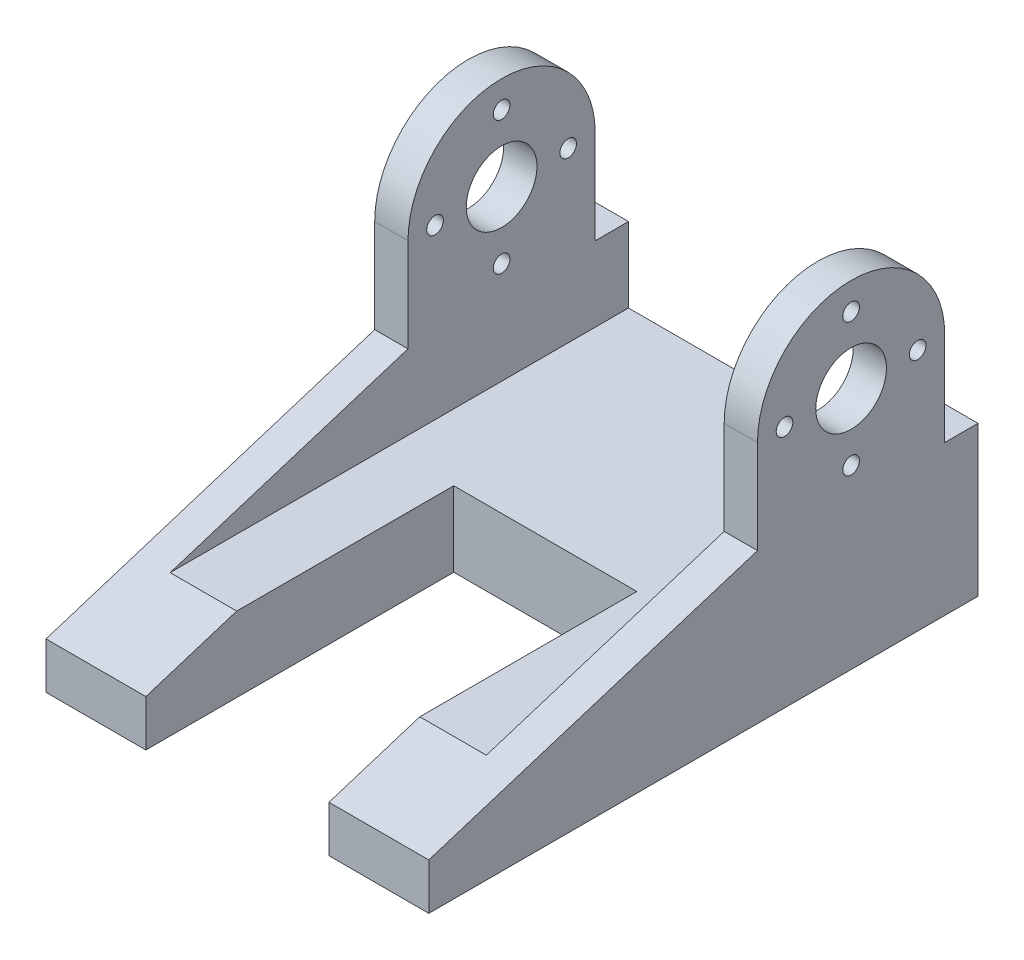
SolidWorks part; units mm, degrees
ref_plane "Front Plane" through (0, 0, 0) normal (0, 0, 1) x (1, 0, 0)
ref_plane "Top Plane" through (0, 0, 0) normal (0, 1, 0) x (1, 0, 0)
ref_plane "Right Plane" through (0, 0, 0) normal (1, 0, 0) x (0, 0, -1)
sketch "Sketch1" plane through (0, 0, 0) normal (0, 0, 1) x (1, 0, 0)
  line L1 (-25, 0) -> (25, 0)
  line L2 (-25, 0) -> (-25, -170)
  line L3 (-25, -170) -> (25, -170)
  line L4 (25, 0) -> (25, -170)
  dimension "D1" = 170
  dimension "D2" = 50
extrude "Boss-Extrude1" add sketch "Sketch1" against normal blind 55
sketch "Sketch2" plane through (0, 0, 0) normal (0, 0, 1) x (1, 0, 0)
  line L0 (25, 0) -> (-25, 0) construction
  line L1 (-17, 0) -> (17, 0)
  line L2 (-17, 0) -> (-17, -27)
  line L3 (-17, -27) -> (17, -27)
  line L4 (17, 0) -> (17, -27)
  line L5 (-25, 0) -> (-25, -170) construction
  dimension "D1" = 8
  dimension "D2" = 34
  dimension "D3" = 27
extrude "Cut-Extrude1" cut sketch "Sketch2" against normal through all
sketch "Sketch3" plane through (25, 0, 0) normal (1, 0, 0) x (0, 0, -1)
  line L0 (0, -170) -> (0, 0) construction
  line L1 (55, -27) -> (0, -27)
  line L2 (55, -27) -> (55, -24)
  line L3 (55, -24) -> (0, -24)
  line L4 (0, -27) -> (0, -24)
  line L5 (55, -170) -> (55, 0) construction
  line L7 (0, 0) -> (10, 0)
  line L8 (0, 0) -> (0, -24)
  line L9 (0, -24) -> (10, -24)
  line L10 (10, 0) -> (10, -24)
  line L11 (55, 0) -> (45, 0)
  line L12 (55, 0) -> (55, -24)
  line L13 (55, -24) -> (45, -24)
  line L14 (45, 0) -> (45, -24)
  circle A0 centre (27.5, -12.75) radius 10.25
  circle A1 centre (27.5, -12.75) radius 4.25
  circle A2 centre (27.5, -12.75) radius 8
  circle A3 centre (27.5, -4.75) radius 1
  circle A4 centre (35.5, -12.75) radius 1
  circle A5 centre (27.5, -20.75) radius 1
  circle A6 centre (19.5, -12.75) radius 1
  point P32 (27.5, -12.75)
  line M7 (0, 0) -> (0, -170)
  line M9 (55, -170) -> (55, 0)
  line M10 (55, 0) -> (0, 0)
  dimension "D2" = 11.25
  dimension "D3" = 27.5
  dimension "D4" = 20.5
  dimension "D7" = 8.5
  dimension "D8" = 16
  dimension "D9" = 4
  dimension "D1" = 3
  dimension "D5" = 10
  dimension "D6" = 10
extrude "Cut-Extrude2" cut sketch "Sketch3" against normal through all contours L14 L3 M10 M9 | L10 L3 M10 M7 | A2 A6 | A2 A6 | A1 | A2 A5 | A2 A5 | A2 A4 | A2 A4 | A2 A3 | A2 A3 region at (25, -12, -50) region at (25, -12, -5) region at (25, -12.75, -27.5) region at (25, -12.75, -35.0645) region at (25, -12.75, -35.913) region at (25, -5.1855, -27.5) region at (25, -4.337, -27.5) region at (25, -21.163, -27.5) region at (25, -20.3145, -27.5) region at (25, -12.75, -19.9355) region at (25, -12.75, -19.087)
sketch "Sketch4" plane through (0, 0, -10) normal (0, 0, 1) x (1, 0, 0)
  line L0 (-25, -24) -> (-17, -24) construction
  line L1 (-17, 0) -> (-19, 0)
  line L2 (-17, 0) -> (-17, -24)
  line L3 (-17, -24) -> (-19, -24)
  line L4 (-19, 0) -> (-19, -24)
  line L5 (0, 0) -> (0, -13.53) construction
  line L6 (19, 0) -> (19, -24)
  line L7 (17, -24) -> (19, -24)
  line L8 (17, 0) -> (17, -24)
  line L9 (17, 0) -> (19, 0)
  dimension "D1" = 2
extrude "Cut-Extrude3" cut sketch "Sketch4" against normal through all
sketch "Sketch5" plane through (25, 0, 0) normal (1, 0, 0) x (0, 0, -1)
  line L1 (10, 0) -> (45, 0)
  line L2 (10, 0) -> (10, -24)
  line L3 (10, -24) -> (45, -24)
  line L4 (45, 0) -> (45, -24)
  line L5 (38.75, -12.75) -> (38.75, -24)
  line L6 (16.25, -12.75) -> (10, -12.75)
  line L7 (16.25, -12.75) -> (16.25, -24)
  line L8 (16.25, -24) -> (10, -24)
  line L9 (10, -12.75) -> (10, -24)
  line L10 (38.75, -12.75) -> (45, -12.75)
  line L11 (38.75, -12.75) -> (38.75, -24)
  line L12 (38.75, -24) -> (45, -24)
  line L13 (45, -12.75) -> (45, -24)
  circle A0 centre (27.5, -12.75) radius 11.25
  line M8 (45, -24) -> (45, 0)
  line M9 (45, 0) -> (10, 0)
  line M10 (10, 0) -> (10, -24)
  dimension "D1" = 22.5
extrude "Cut-Extrude4" cut sketch "Sketch5" against normal through all contours A0 L10 L4 L6 M9 M10 | L7 L6 L2 L3 | L10 L5 L3 M8 region at (25, -0.3725, -27.5) region at (25, -18.375, -13.125) region at (25, -18.375, -41.875)
sketch "Sketch6" plane through (0, 0, 0) normal (0, 0, 1) x (1, 0, 0)
  line L1 (-19, -24) -> (19, -24)
  line L2 (-19, -24) -> (-19, -34)
  line L3 (-19, -34) -> (19, -34)
  line L4 (19, -24) -> (19, -34)
  dimension "D1" = 10
extrude "Cut-Extrude5" cut sketch "Sketch6" against normal through all
sketch "Sketch8" plane through (25, 0, 0) normal (1, 0, 0) x (0, 0, -1)
  line L0 (55, -170) -> (55, -24) construction
  line L1 (0, -170) -> (0, -24) construction
  line L2 (41.75, -132.5) -> (13.25, -132.5)
  line L3 (27.5, -132.5) -> (27.5, -179)
  line L4 (41.75, -179) -> (13.25, -179)
  line L5 (13.25, -132.5) -> (13.25, -179)
  line L7 (41.75, -132.5) -> (41.75, -179)
  line L11 (27.5, -167.75) -> (55, -167.75)
  line L12 (27.5, -167.75) -> (27.5, -170)
  line L13 (27.5, -170) -> (55, -170)
  line L14 (55, -167.75) -> (55, -170)
  line L16 (27.5, -167.75) -> (0, -167.75)
  line L17 (27.5, -167.75) -> (27.5, -170)
  line L18 (27.5, -170) -> (0, -170)
  line L19 (0, -167.75) -> (0, -170)
  circle A0 centre (27.5, -167.75) radius 10.25
  circle A1 centre (27.5, -12.75) radius 10.25
  line M4 (0, -24) -> (0, -170)
  line M5 (0, -170) -> (55, -170)
  line M6 (55, -170) -> (55, -24)
  dimension "D1" = 27.5
  dimension "D2" = 20.5
  dimension "D3" = 155
  dimension "D4" = 14.25
  dimension "D5" = 11.25
  dimension "D6" = 46.5
  dimension "D7" = 13.25
extrude "Cut-Extrude7" cut sketch "Sketch8" against normal through all contours A0 L3 L2 L5 L16 | A0 L11 L7 L2 L3 | L11 L7 M5 M6 | L5 L16 M4 M5 | A0 L16 L5 M5 | A0 L13 L7 L11 | L3 A0 L16 | L11 A0 L3 | L16 A0 L18 L3 | A0 L11 L3 M5 region at (25, -147.5157, -35.1704) region at (25, -147.5157, -19.8296) region at (25, -168.875, -48.375) region at (25, -168.8865, -39.7079) region at (25, -163.3998, -31.8502) region at (25, -163.3998, -23.1498) region at (25, -168.8704, -32.5838) region at (25, -168.8865, -15.2921) region at (25, -168.875, -6.625) region at (25, -168.8704, -22.4162)
sketch "Sketch9" plane through (0, 0, 0) normal (0, 0, 1) x (1, 0, 0)
  line L0 (-25, -167.75) -> (25, -167.75) construction
  line L1 (17, -167.75) -> (-17, -167.75)
  line L2 (17, -167.75) -> (17, -132.5)
  line L3 (17, -132.5) -> (-17, -132.5)
  line L4 (-17, -167.75) -> (-17, -132.5)
  line L5 (-25, -132.5) -> (25, -132.5) construction
  line L7 (-25, -24) -> (-25, -167.75) construction
  line L9 (25, -167.75) -> (25, -24) construction
  dimension "D1" = 8
  dimension "D2" = 8
extrude "Cut-Extrude8" cut sketch "Sketch9" against normal through all
sketch "Sketch11" plane through (25, 0, 0) normal (1, 0, 0) x (0, 0, -1)
  line L0 (27.5, -157.5) -> (27.5, -147.5)
  line L2 (27.5, -147.5) -> (55, -147.5)
  line L3 (27.5, -147.5) -> (27.5, -167.75)
  line L4 (27.5, -167.75) -> (55, -167.75)
  line L5 (55, -147.5) -> (55, -167.75)
  line L6 (27.5, -147.5) -> (0, -147.5)
  line L7 (27.5, -147.5) -> (27.5, -167.75)
  line L8 (27.5, -167.75) -> (0, -167.75)
  line L9 (0, -147.5) -> (0, -167.75)
  circle A0 centre (27.5, -167.75) radius 10.25
  arc A1 (38.75, -12.75) -> (16.25, -12.75) centre (27.5, -12.75) ccw construction
  line M1 (0, -167.75) -> (13.25, -167.75)
  line M2 (13.25, -167.75) -> (13.25, -132.5)
  line M4 (41.75, -132.5) -> (41.75, -167.75)
  line M5 (41.75, -167.75) -> (55, -167.75)
  line M6 (55, -167.75) -> (55, -24)
  line M12 (0, -24) -> (0, -167.75)
  dimension "D1" = 155
  dimension "D2" = 20.5
  dimension "D3" = 10
extrude "Cut-Extrude9" cut sketch "Sketch11" against normal through all contours A0 L0 L6 L8 M2 | A0 L4 L2 L0 M4 | L2 M4 M5 M6 | L6 M2 M12 M1 region at (25, -155.3124, -19.2638) region at (25, -155.3124, -35.7362) region at (25, -157.625, -48.375) region at (25, -157.625, -6.625)
sketch "Sketch12" plane through (25, 0, 0) normal (1, 0, 0) x (0, 0, -1)
  line L1 (13.25, -132.5) -> (41.75, -132.5)
  line L2 (13.25, -132.5) -> (13.25, -147.5)
  line L3 (13.25, -147.5) -> (41.75, -147.5)
  line L4 (41.75, -132.5) -> (41.75, -147.5)
extrude "Boss-Extrude2" add sketch "Sketch12" against normal blind 8
ref_plane "Plane1" through (0, 0, 0) normal (1, 0, 0) x (0, 0, -1)
mirror "Mirror1" about plane through (0, 0, 0) normal (1, 0, 0) of "Boss-Extrude2"
sketch "Sketch14" plane through (0, 0, 0) normal (0, 0, 1) x (1, 0, 0)
  line L0 (17, -148.55) -> (17, -158.75) construction
  line L1 (-17, -132.5) -> (17, -132.5)
  line L2 (-17, -132.5) -> (-17, -147.5)
  line L3 (-17, -147.5) -> (17, -147.5)
  line L4 (17, -132.5) -> (17, -147.5)
  line L5 (-17, -147.5) -> (17, -147.5)
  line L6 (-17, -147.5) -> (-17, -157.75)
  line L7 (-17, -157.75) -> (17, -157.75)
  line L8 (17, -147.5) -> (17, -157.75)
  line M11 (-17, -147.5) -> (-17, -132.5)
  line M12 (-17, -132.5) -> (17, -132.5)
  line M13 (17, -132.5) -> (17, -147.5)
  dimension "D1" = 10.25
extrude "Boss-Extrude3" add sketch "Sketch14" against normal blind 13.25 contours L3 M11 M13 M12 | L8 L3 L6 L7 region at (0, -140, 0) region at (0, -152.625, 0)
ref_plane "Plane2" through (0, 0, -27.5) normal (0, 0, 1) x (1, 0, 0)
mirror "Mirror2" about plane through (0, 0, -27.5) normal (0, 0, 1) of "Boss-Extrude3"
sketch "Sketch16" plane through (25, 0, 0) normal (1, 0, 0) x (0, 0, -1)
  line L0 (41.75, -132.5) -> (13.25, -132.5) construction
  line L1 (13.25, -132.5) -> (13.25, -147.5) construction
  circle A1 centre (16.5, -135.75) radius 2.5
  circle A2 centre (16.5, -135.75) radius 4.5
  circle A3 centre (38.5, -135.75) radius 4.5
  dimension "D1" = 3.25
  dimension "D2" = 3.25
  dimension "D3" = 2
extrude "Cut-Extrude13" cut sketch "Sketch16" against normal blind 8 contours A1 | A2 A1 | A3 region at (25, -135.75, -16.5) region at (25, -135.75, -12.1273) region at (25, -135.75, -38.5)
mirror "Mirror3" about plane through (0, 0, 0) normal (1, 0, 0) of "Cut-Extrude13"
sketch "Sketch17" plane through (25, 0, 0) normal (1, 0, 0) x (0, 0, -1)
  line L0 (55, -147.5) -> (55, -24) construction
  line L1 (27.5, -1.5) -> (55, -1.5)
  line L2 (27.5, -1.5) -> (27.5, -51.5)
  line L3 (27.5, -51.5) -> (55, -51.5)
  line L4 (55, -1.5) -> (55, -51.5)
  line L8 (55, -51.5) -> (0, -51.5)
  line L9 (55, -51.5) -> (55, -157.75)
  line L10 (55, -157.75) -> (0, -157.75)
  line L11 (0, -51.5) -> (0, -157.75)
  arc A0 (38.75, -12.75) -> (16.25, -12.75) centre (27.5, -12.75) ccw construction
  circle M2 centre (16.5, -135.75) radius 4.5
  circle M3 centre (38.5, -135.75) radius 4.5
  line M4 (0, -147.5) -> (55, -147.5)
  line M5 (55, -147.5) -> (55, -24)
  line M11 (0, -24) -> (0, -147.5)
  dimension "D1" = 50
extrude "Cut-Extrude15" cut sketch "Sketch17" against normal through all contours L3 L8 M11 M4 M5 M2 M3 | L11 L10 L9 M4 | M3 | M2 region at (25, -98.6049, -27.5) region at (25, -152.625, -27.5) region at (25, -135.75, -16.5) region at (25, -135.75, -38.5)
sketch "Sketch18" plane through (25, 0, 0) normal (1, 0, 0) x (0, 0, -1)
  line L1 (38.75, -24) -> (-71.25, -24)
  line L2 (38.75, -24) -> (38.75, -51.5)
  line L3 (38.75, -51.5) -> (-71.25, -51.5)
  line L4 (-71.25, -24) -> (-71.25, -51.5)
  line L6 (38.75, -24) -> (68.75, -24)
  line L7 (38.75, -24) -> (38.75, -51.5)
  line L8 (38.75, -51.5) -> (68.75, -51.5)
  line L9 (68.75, -24) -> (68.75, -51.5)
  line M8 (0, -24) -> (0, -51.5)
  line M9 (0, -51.5) -> (55, -51.5)
  line M10 (55, -51.5) -> (55, -24)
  line M11 (55, -24) -> (38.75, -24)
  line M15 (16.25, -24) -> (0, -24)
  dimension "D1" = 110
  dimension "D2" = 30
extrude "Boss-Extrude4" add sketch "Sketch18" against normal blind 50 contours L1 L4 L3 M8 | L9 L6 L8 M10 | L2 L1 M15 M8 M9 | L2 M11 M9 M10 region at (25, -37.75, -19.375) region at (25, -37.75, -46.875) region at (25, -37.75, -61.875) region at (25, -37.75, 35.625)
sketch "Sketch19" plane through (0, 0, 71.25) normal (0, 0, 1) x (1, 0, 0)
  line L1 (-19, -24) -> (19, -24)
  line L2 (-19, -24) -> (-19, -31)
  line L3 (-19, -31) -> (19, -31)
  line L4 (19, -24) -> (19, -31)
  dimension "D1" = 7
extrude "Cut-Extrude16" cut sketch "Sketch19" against normal through all
sketch "Sketch20" plane through (25, 0, 0) normal (1, 0, 0) x (0, 0, -1)
  line L1 (-71.25, -24) -> (68.75, -24)
  line L2 (-71.25, -24) -> (-71.25, -51.5)
  line L3 (-71.25, -51.5) -> (68.75, -51.5)
  line L4 (68.75, -24) -> (68.75, -51.5)
  line L5 (16.25, -24) -> (-13.75, -24)
  line L6 (16.25, -24) -> (16.25, -51.5)
  line L7 (16.25, -51.5) -> (-13.75, -51.5)
  line L8 (-13.75, -24) -> (-13.75, -51.5)
  line L10 (-13.75, -51.5) -> (-71.25, -51.5)
  line L11 (-13.75, -51.5) -> (-13.75, -24)
  line L12 (-13.75, -24) -> (-71.25, -24)
  line L13 (-71.25, -51.5) -> (-71.25, -24)
  line M8 (-71.25, -24) -> (-71.25, -51.5)
  line M9 (-71.25, -51.5) -> (68.75, -51.5)
  dimension "D1" = 30
extrude "Cut-Extrude17" cut sketch "Sketch20" against normal through all contours L8 L1 M8 M9 region at (25, -37.75, 42.5)
sketch "Sketch21" plane through (25, 0, 0) normal (1, 0, 0) x (0, 0, -1)
  line L0 (16.25, -24) -> (-13.75, -51.5)
  line L1 (16.25, -24) -> (-13.75, -24)
  line L2 (16.25, -24) -> (16.25, -51.5)
  line L3 (16.25, -51.5) -> (-13.75, -51.5)
  line L4 (-13.75, -24) -> (-13.75, -51.5)
  line M6 (16.25, -24) -> (-13.75, -24)
  line M7 (-13.75, -24) -> (-13.75, -51.5)
extrude "Cut-Extrude18" cut sketch "Sketch21" against normal through all contours L0 M6 M7 region at (25, -33.1667, 3.75)
sketch "Sketch22" plane through (25, 0, 0) normal (1, 0, 0) x (0, 0, -1)
  line L3 (68.75, -51.5) -> (-13.75, -51.5)
  line L4 (68.75, -51.5) -> (68.75, -54)
  line L5 (68.75, -54) -> (-13.75, -54)
  line L6 (-13.75, -51.5) -> (-13.75, -54)
  dimension "D1" = 2.5
extrude "Boss-Extrude5" add sketch "Sketch22" against normal blind 50
sketch "Sketch24" plane through (25, 0, 0) normal (1, 0, 0) x (0, 0, -1)
  line L1 (68.75, -24) -> (46.75, -24)
  line L2 (68.75, -24) -> (68.75, -41)
  line L3 (68.75, -41) -> (46.75, -41)
  line L4 (46.75, -24) -> (46.75, -41)
  dimension "D1" = 17
  dimension "D2" = 22
extrude "Cut-Extrude19" cut sketch "Sketch24" against normal through all
sketch "Sketch25" plane through (0, -31, 0) normal (0, 1, 0) x (1, 0, 0)
  line L1 (-19, 46.75) -> (19, 46.75)
  line L2 (-19, 46.75) -> (-19, 8.6136)
  line L3 (-19, 8.6136) -> (19, 8.6136)
  line L4 (19, 46.75) -> (19, 8.6136)
extrude "Cut-Extrude20" cut sketch "Sketch25" against normal blind 10
sketch "Sketch27" plane through (0, -41, 0) normal (0, 1, 0) x (1, 0, 0)
  line L0 (-25, 68.75) -> (25, 68.75) construction
  line L1 (19, 8.6136) -> (-19, 8.6136)
  line L2 (19, 8.6136) -> (19, 68.75)
  line L3 (19, 68.75) -> (-19, 68.75)
  line L4 (-19, 8.6136) -> (-19, 68.75)
extrude "Boss-Extrude6" add sketch "Sketch27" along normal blind 8.6
sketch "Sketch29" plane through (0, 0, -8.6136) normal (0, 0, -1) x (-1, 0, 0)
  line L1 (-19, -31) -> (19, -31)
  line L2 (-19, -31) -> (-19, -32.4)
  line L3 (-19, -32.4) -> (19, -32.4)
  line L4 (19, -31) -> (19, -32.4)
extrude "Cut-Extrude21" cut sketch "Sketch29" against normal through all
sketch "Sketch30" plane through (-25, 0, 0) normal (-1, 0, 0) x (0, 0, 1)
  line L0 (-68.75, -32.4) -> (-68.75, -41) construction
  line L1 (-38.75, -24) -> (31.25, -24)
  line L2 (-38.75, -24) -> (-38.75, -53.9144)
  line L3 (-38.75, -53.9144) -> (31.25, -53.9144)
  line L4 (31.25, -24) -> (31.25, -53.9144)
  line L5 (-16.25, -24) -> (31.25, -38.9572)
  line L6 (31.25, -38.9572) -> (31.25, -53.9144)
  line L7 (-16.25, -24) -> (-16.25, -32.4)
  line L8 (-46.75, -32.4) -> (-7.0864, -32.4) construction
  line L9 (-16.25, -32.4) -> (-7.0864, -32.4)
  line L10 (-7.0864, -32.4) -> (-16.25, -24)
  line M5 (13.75, -54) -> (13.75, -51.5)
  line M6 (13.75, -51.5) -> (-16.25, -24)
  dimension "D1" = 100
extrude "Boss-Extrude7" add sketch "Sketch30" against normal blind 50 contours L5 L3 L4 M6 M5 | L7 L9 L10 region at (-25, -40.9436, 13.5151)
sketch "Sketch31" plane through (0, 0, -68.75) normal (0, 0, -1) x (-1, 0, 0)
  line L1 (-19, -24) -> (19, -24)
  line L2 (-19, -24) -> (-19, -41)
  line L3 (-19, -41) -> (19, -41)
  line L4 (19, -24) -> (19, -41)
extrude "Cut-Extrude22" cut sketch "Sketch31" against normal through all
sketch "Sketch32" plane through (25, 0, 0) normal (1, 0, 0) x (0, 0, -1)
  line L0 (-31.25, -38.9572) -> (-31.25, -53.9144) construction
  line L1 (68.75, -54) -> (-31.25, -54)
  line L2 (68.75, -54) -> (68.75, -51)
  line L3 (68.75, -51) -> (-31.25, -51)
  line L4 (-31.25, -54) -> (-31.25, -51)
  dimension "D1" = 3
extrude "Cut-Extrude23" cut sketch "Sketch32" against normal through all
sketch "Sketch33" plane through (0, -41, 0) normal (0, 1, 0) x (1, 0, 0)
  line L0 (19, -31.25) -> (-19, -31.25) construction
  line L1 (11, -31.25) -> (-11, -31.25)
  line L2 (11, -31.25) -> (11, 13.75)
  line L3 (11, 13.75) -> (-11, 13.75)
  line L4 (-11, -31.25) -> (-11, 13.75)
  line L6 (-25, 68.75) -> (-10, 68.75)
  line L7 (-25, 68.75) -> (-25, 46.75)
  line L8 (-25, 46.75) -> (-10, 46.75)
  line L9 (-10, 68.75) -> (-10, 46.75)
  line L10 (25, 68.75) -> (10, 68.75)
  line L11 (25, 68.75) -> (25, 46.75)
  line L12 (25, 46.75) -> (10, 46.75)
  line L13 (10, 68.75) -> (10, 46.75)
  line L15 (19, 16.25) -> (19, -31.25) construction
  line L16 (-19, -31.25) -> (-19, 46.75) construction
  line L18 (-10, 68.75) -> (10, 68.75)
  line L19 (-10, 68.75) -> (-10, 58.75)
  line L20 (-10, 58.75) -> (10, 58.75)
  line L21 (10, 68.75) -> (10, 58.75)
  line M10 (-25, 46.75) -> (-19, 46.75)
  line M12 (-19, -31.25) -> (19, -31.25)
  line M14 (19, 46.75) -> (25, 46.75)
  line M15 (25, 46.75) -> (25, 68.75)
  line M16 (25, 68.75) -> (-25, 68.75)
  line M17 (-25, 68.75) -> (-25, 46.75)
  dimension "D1" = 8
  dimension "D2" = 8
  dimension "D3" = 45
  dimension "D4" = 15
  dimension "D5" = 15
  dimension "D6" = 10
extrude "Cut-Extrude24" cut sketch "Sketch33" against normal through all contours L9 L8 M16 M17 M10 | L13 L12 M16 M14 M15 | L9 L20 L13 M16 | L4 L2 L3 M12 region at (0, -41, 8.75) region at (-17.5, -41, -57.75) region at (0, -41, -63.75) region at (17.5, -41, -57.75)
sketch "Sketch34" plane through (0, -41, 0) normal (0, 1, 0) x (1, 0, 0)
  line L0 (-10, 58.75) -> (10, 58.75) construction
  line L1 (-4, 58.75) -> (4, 58.75)
  line L2 (-4, 58.75) -> (-4, 46.75)
  line L3 (-4, 46.75) -> (4, 46.75)
  line L4 (4, 58.75) -> (4, 46.75)
  line L5 (-10, 58.75) -> (-10, 46.75) construction
  line L6 (10, 58.75) -> (10, 46.75) construction
  dimension "D1" = 6
  dimension "D2" = 6
  dimension "D3" = 12
extrude "Cut-Extrude25" cut sketch "Sketch34" against normal through all
sketch "Sketch36" plane through (0, -41, 0) normal (0, 1, 0) x (1, 0, 0)
  line L1 (19, -31.25) -> (-19, -31.25)
  line L2 (19, -31.25) -> (19, 58.75)
  line L3 (19, 58.75) -> (-19, 58.75)
  line L4 (-19, -31.25) -> (-19, 58.75)
  line L5 (-4, 58.75) -> (4, 58.75)
  line L6 (-4, 58.75) -> (-4, 46.75)
  line L7 (-4, 46.75) -> (4, 46.75)
  line L8 (4, 58.75) -> (4, 46.75)
  line L9 (10, 58.75) -> (19, 58.75)
  line L10 (10, 58.75) -> (10, 46.75)
  line L11 (10, 46.75) -> (19, 46.75)
  line L12 (19, 58.75) -> (19, 46.75)
  line L13 (-10, 58.75) -> (-19, 58.75)
  line L14 (-10, 58.75) -> (-10, 46.75)
  line L15 (-10, 46.75) -> (-19, 46.75)
  line L16 (-19, 58.75) -> (-19, 46.75)
  line L17 (-11, 13.75) -> (11, 13.75)
  line L18 (-11, 13.75) -> (-11, -31.25)
  line L19 (-11, -31.25) -> (11, -31.25)
  line L20 (11, 13.75) -> (11, -31.25)
  line M1 (4, 46.75) -> (-4, 46.75)
  line M2 (-4, 46.75) -> (-4, 58.75)
  line M3 (-4, 58.75) -> (-10, 58.75)
  line M4 (-10, 58.75) -> (-10, 46.75)
  line M5 (-10, 46.75) -> (-19, 46.75)
  line M6 (-19, 46.75) -> (-19, -31.25)
  line M7 (-19, -31.25) -> (-11, -31.25)
  line M8 (-11, -31.25) -> (-11, 13.75)
  line M9 (-11, 13.75) -> (11, 13.75)
  line M10 (11, 13.75) -> (11, -31.25)
  line M11 (11, -31.25) -> (19, -31.25)
  line M12 (19, -31.25) -> (19, 46.75)
  line M13 (19, 46.75) -> (10, 46.75)
  line M14 (10, 46.75) -> (10, 58.75)
  line M15 (10, 58.75) -> (4, 58.75)
  line M16 (4, 58.75) -> (4, 46.75)
extrude "Boss-Extrude8" add sketch "Sketch36" along normal blind 8 contours M16 M1 M2 M3 M4 M5 M6 M7 M8 M9 M10 M11 M12 M13 M14 M15 region at (0, -41, -18.522)
sketch "Sketch37" plane through (25, 0, 0) normal (1, 0, 0) x (0, 0, -1)
  line L0 (-31.25, -38.9572) -> (-31.25, -51) construction
  line L1 (58.75, -51) -> (-31.25, -51)
  line L2 (58.75, -51) -> (58.75, -42)
  line L3 (58.75, -42) -> (-31.25, -42)
  line L4 (-31.25, -51) -> (-31.25, -42)
  line L5 (-31.25, -38.9572) -> (-12.3315, -33)
  line L6 (-12.3315, -33) -> (-31.25, -33)
  line L7 (-12.3315, -33) -> (-12.3315, -38.9572)
  line L8 (-12.3315, -38.9572) -> (-31.25, -38.9572)
  line L9 (-31.25, -33) -> (-31.25, -38.9572)
  line L11 (58.75, -42) -> (46.75, -42)
  line L12 (58.75, -42) -> (58.75, -51)
  line L13 (58.75, -51) -> (46.75, -51)
  line L14 (46.75, -42) -> (46.75, -51)
  line M7 (-31.25, -51) -> (46.75, -51)
  line M8 (46.75, -51) -> (46.75, -24)
  line M13 (16.25, -24) -> (-31.25, -38.9572)
  line M14 (-31.25, -38.9572) -> (-31.25, -51)
  dimension "D1" = 9
extrude "Cut-Extrude27" cut sketch "Sketch37" against normal through all contours L3 M8 M14 M7 | L6 L9 M13 | L2 L3 L1 M8 region at (25, -34.9857, 24.9438) region at (25, -46.5, -52.75) region at (25, -46.5, -7.75)
fillet "Fillet1" radius 10 2 edges at (-7, -42, -58.75) (7, -42, -58.75)
sketch "Sketch38" plane through (0, 0, 0) normal (0, 1, 0) x (1, 0, 0)
  line L6 (-11, -31.25) -> (-25, -31.25) construction
  line L7 (-25, 46.75) -> (-23, 46.75)
  line L8 (-25, 46.75) -> (-25, -31.25)
  line L9 (-25, -31.25) -> (-23, -31.25)
  line L10 (-23, 46.75) -> (-23, -31.25)
  line L11 (25, -31.25) -> (11, -31.25) construction
  line L12 (25, 46.75) -> (23, 46.75)
  line L13 (25, 46.75) -> (25, -31.25)
  line L14 (25, -31.25) -> (23, -31.25)
  line L15 (23, 46.75) -> (23, -31.25)
  line L17 (-23, -31.25) -> (23, -31.25)
  line L18 (-23, -31.25) -> (-23, -23.25)
  line L19 (-23, -23.25) -> (23, -23.25)
  line L20 (23, -31.25) -> (23, -23.25)
  dimension "D1" = 2
  dimension "D2" = 2
  dimension "D3" = 8
extrude "Cut-Extrude29" cut sketch "Sketch38" against normal through all both and the other way through all contours L10 L7 L8 L9 | L12 L15 L14 L13 | L19 L10 L17 L15 region at (-24, 0, -7.75) region at (0, 0, 27.25) region at (24, 0, -7.75)
sketch "Sketch39" plane through (23, 0, 0) normal (1, 0, 0) x (0, 0, -1)
  line L0 (46.75, -24) -> (38.75, -24) construction
  line L1 (42.75, -24) -> (64.9734, -24)
  line L2 (42.75, -24) -> (42.75, -43.4413)
  line L3 (42.75, -43.4413) -> (64.9734, -43.4413)
  line L4 (64.9734, -24) -> (64.9734, -43.4413)
extrude "Cut-Extrude30" cut sketch "Sketch39" against normal through all
